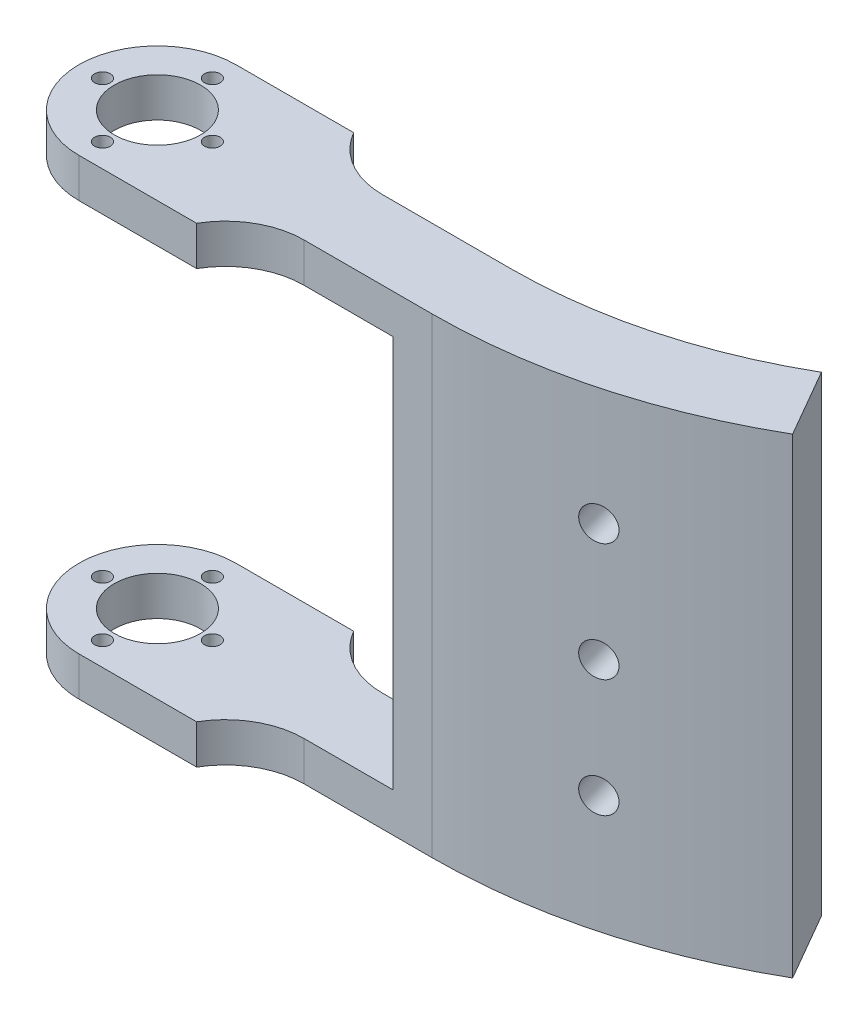
SolidWorks part; units mm, degrees
ref_plane "Front Plane" through (0, 0, 0) normal (0, 0, 1) x (1, 0, 0)
ref_plane "Top Plane" through (0, 0, 0) normal (0, 1, 0) x (1, 0, 0)
ref_plane "Right Plane" through (0, 0, 0) normal (1, 0, 0) x (0, 0, -1)
sketch "Sketch1" plane through (0, 0, 0) normal (0, 0, 1) x (1, 0, 0)
  line L0 (-25, 30) -> (25, 30)
  line L1 (-20, 25) -> (20, 25)
  line L3 (-20, -25) -> (20, -25)
  line L4 (20, 25) -> (20, -25)
  line L5 (-20, 25) -> (20, -25) construction
  line L6 (-20, -25) -> (20, 25) construction
  line L7 (25, 30) -> (25, -30)
  line L8 (-25, -30) -> (25, -30)
  line L9 (-25, 30) -> (-25, 25)
  line L10 (-20, 25) -> (-25, 25)
  line L11 (-20, -25) -> (-25, -25)
  line L12 (-25, -25) -> (-25, -30)
  line L13 (-25, 30) -> (-25, -30) construction
  line L14 (-20, 25) -> (-20, -25) construction
  point P0 (0, 0)
  dimension "D1" = 40
  dimension "D2" = 50
  dimension "D3" = 5
extrude "Boss-Extrude2" add sketch "Sketch1" along normal blind 20
fillet "Fillet1" 2 edges at (-25, 27.5, 20) (-25, 27.5, 0) type full round first side face at (-1.25, 0, 20) second side face at (-1.25, 0, 0) middle face at (-25, 27.5, 10)
fillet "Fillet2" 2 edges at (-25, -27.5, 20) (-25, -27.5, 0) type full round first side face at (1.25, 0, 20) second side face at (1.25, 0, 0) middle face at (-25, -27.5, 10)
sketch "Sketch5" plane through (0, 30, 0) normal (0, 1, 0) x (1, 0, 0)
  circle A0 centre (-15, -10) radius 7 construction
  circle A1 centre (-15, -3) radius 1
  circle A2 centre (-22, -10) radius 1
  circle A3 centre (-15, -17) radius 1
  circle A4 centre (-8, -10) radius 1
  circle A5 centre (-15, -10) radius 5.5
  dimension "D1" = 14
  dimension "D2" = 2
  dimension "D3" = 11
extrude "Cut-Extrude5" cut sketch "Sketch5" against normal through all
sketch "Sketch10" plane through (25, 0, 0) normal (1, 0, 0) x (0, 0, -1)
  line L1 (-15, 28.1801) -> (-15, -28.1801)
  line L3 (-20, -30) -> (-20, 30) construction
  line L4 (-10, 30) -> (-10, 19.211) construction
  line L5 (-20, 30) -> (0, 30) construction
  line L7 (-5, 28.1801) -> (-5, -28.1801)
  line L9 (0, -30) -> (0, 30) construction
  line L10 (0, -30) -> (0, 30)
  line L11 (-20, -30) -> (-20, 30)
  line L12 (-15, 28.1801) -> (-15, 30)
  line L13 (-15, 30) -> (-20, 30)
  line L14 (-15, -28.1801) -> (-15, -30)
  line L15 (-20, -30) -> (0, -30) construction
  line L16 (-15, -30) -> (-20, -30)
  line L17 (-5, -28.1801) -> (-5, -30)
  line L18 (-5, -30) -> (0, -30)
  line L19 (-5, 28.1801) -> (-5, 30)
  line L20 (-5, 30) -> (0, 30)
  dimension "D2" = 5
extrude "Cut-Extrude7" cut sketch "Sketch10" against normal blind 25
fillet "Fillet5" radius 10 4 edges at (0, 27.5, 15) (0, 27.5, 5) (0, -27.5, 15) (0, -27.5, 5)
sketch "Sketch12" plane through (0, -30, 0) normal (0, -1, 0) x (1, 0, 0)
  line L0 (56.2263, -3.3597) -> (61.2225, 5.3027)
  line L1 (25, 15) -> (25, 5)
  arc A0 (56.2263, -3.3597) -> (25, 5) centre (25, -57.5) ccw
  arc A1 (61.2225, 5.3027) -> (25, 15) centre (25, -57.5) ccw
extrude "Boss-Extrude5" add sketch "Sketch12" against normal up to surface (60 mm away) up to face at (-16, 30, 3)
ref_plane "Plane1" through (2.921, 0, 10.9109) normal (-0.2586, 0, -0.966) x (-0.966, 0, 0.2586)
sketch "Sketch13" plane through (2.921, 0, 10.9109) normal (-0.2586, 0, -0.966) x (-0.966, 0, 0.2586)
  line L0 (-39.0195, 30) -> (-39.0195, 0) construction
  line L1 (-22.8565, 30) -> (-55.1825, 30) construction
  line L2 (-39.0195, 0) -> (-39.0195, -30) construction
  line L3 (-55.1825, -30) -> (-22.8565, -30) construction
  circle A0 centre (-39.0195, 15) radius 2.1
  circle A1 centre (-39.0195, 0) radius 2.1
  circle A2 centre (-39.0195, -15) radius 2.1
  dimension "D1" = 4.2
extrude "Cut-Extrude8" cut sketch "Sketch13" against normal blind 60
ref_plane "Plane2" through (4.3924, 0, 18.6716) normal (-0.229, 0, -0.9734) x (-0.9734, 0, 0.229)
ref_plane "Plane3" through (5.1366, 0, 21.8352) normal (-0.229, 0, -0.9734) x (-0.9734, 0, 0.229)
equation "\"éà\"=10"
